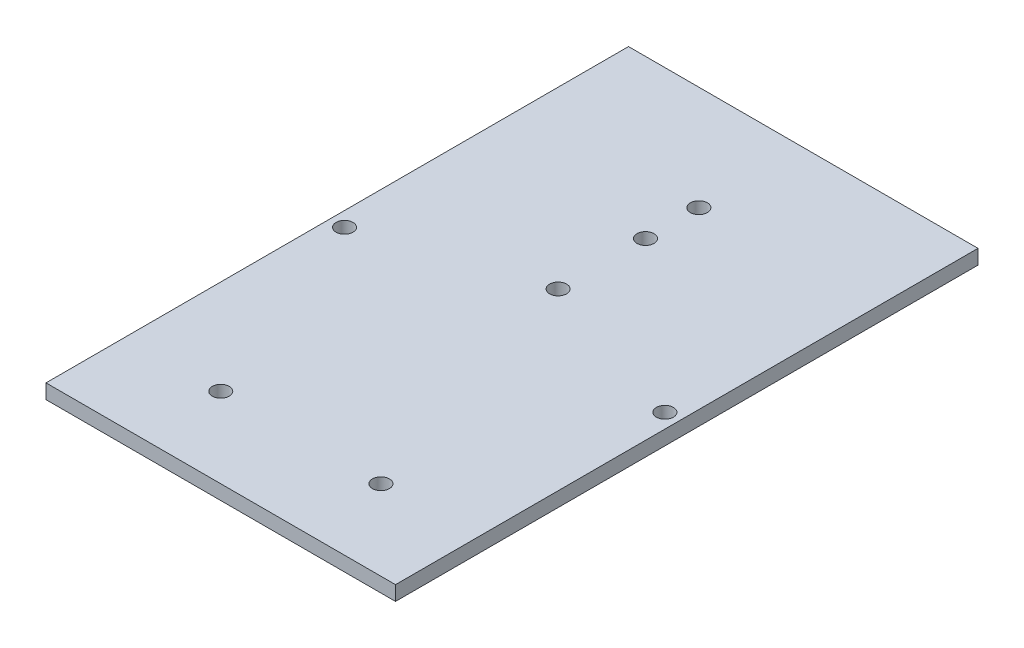
SolidWorks part; units mm, degrees
ref_plane "Front Plane" through (0, 0, 0) normal (0, 0, 1) x (1, 0, 0)
ref_plane "Top Plane" through (0, 0, 0) normal (0, 1, 0) x (1, 0, 0)
ref_plane "Right Plane" through (0, 0, 0) normal (1, 0, 0) x (0, 0, -1)
sketch "Sketch1" plane through (0, 0, 0) normal (0, 1, 0) x (1, 0, 0)
  line L0 (0, 0) -> (0, 50000) construction
  line L1 (36, -60) -> (-36, -60)
  line L2 (36, -60) -> (36, 60)
  line L3 (36, 60) -> (-36, 60)
  line L4 (-36, -60) -> (-36, 60)
  line L5 (36, -60) -> (-36, 60) construction
  line L6 (36, 60) -> (-36, -60) construction
  line L8 (0, 9.5) -> (0, -1.5)
  line L9 (0, 0) -> (50000, 0) construction
  circle A0 centre (-33, -1.5) radius 1.75
  circle A1 centre (33, -1.5) radius 1.75
  circle A2 centre (-16.5, -43.5) radius 1.75
  circle A3 centre (16.5, -43.5) radius 1.75
  circle A4 centre (0, 27.5) radius 1.75
  circle A5 centre (0, 9.5) radius 1.75
  circle A10 centre (0, 38.5) radius 1.75
  point P0 (0, 0)
  point P27 (-16.75, -55)
  point P29 (36, 0)
  dimension "D3" = 3.5
  dimension "D4" = 3.5
  dimension "D5" = 33
  dimension "D6" = 3.5
  dimension "D7" = 3.5
  dimension "D10" = 3.5
  dimension "D11" = 3.5
  dimension "D19" = 66
  dimension "D1" = 120
  dimension "D2" = 72
  dimension "D8" = 42
  dimension "D9" = 16.5
  dimension "D13" = 18
  dimension "D14" = 11
extrude "Boss-Extrude1" add sketch "Sketch1" along normal blind 3 contours L4 L1 L2 L3 A5 A4 A3 A2 A1 A0 region at (0, 0, 58.6006)
